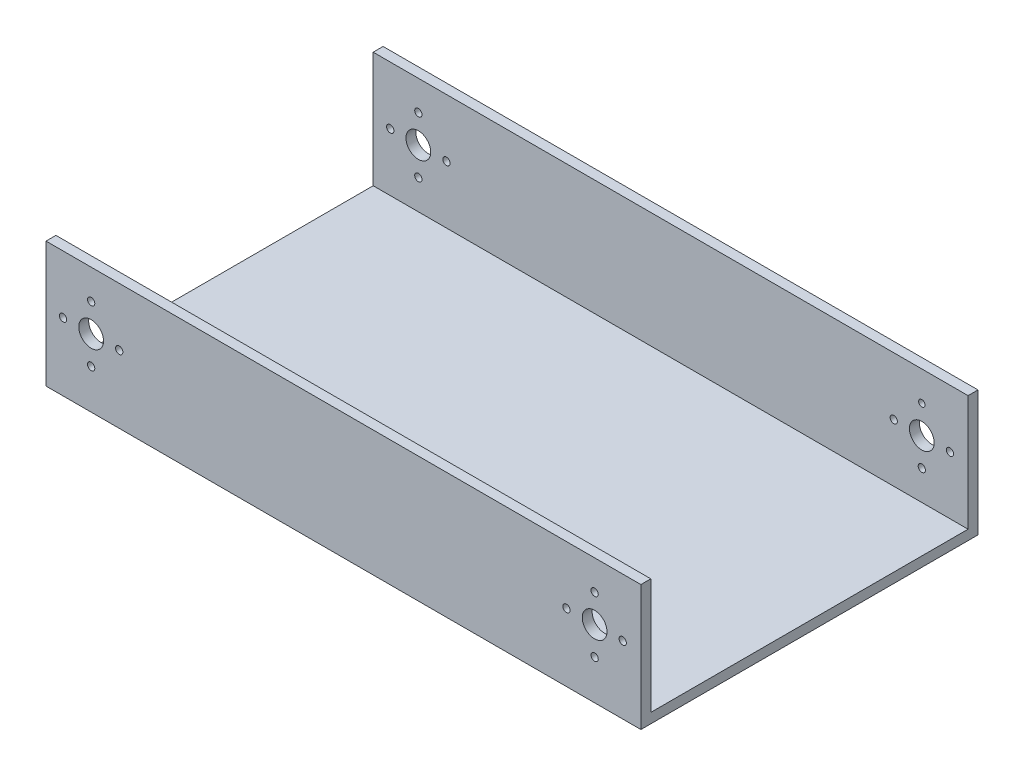
SolidWorks part; units mm, degrees
ref_plane "Front Plane" through (0, 0, 0) normal (0, 0, 1) x (1, 0, 0)
ref_plane "Top Plane" through (0, 0, 0) normal (0, 1, 0) x (1, 0, 0)
ref_plane "Right Plane" through (0, 0, 0) normal (1, 0, 0) x (0, 0, -1)
sketch "스케치1" plane through (0, 0, 0) normal (0, 0, 1) x (1, 0, 0)
  line L1 (-90, 17.5) -> (90, 17.5)
  line L2 (-90, 17.5) -> (-90, -17.5)
  line L3 (-90, -17.5) -> (90, -17.5)
  line L4 (90, 17.5) -> (90, -17.5)
  dimension "D1" = 17.5
  dimension "D2" = 35
  dimension "D3" = 90
  dimension "D4" = 180
extrude "보스-돌출1" add sketch "스케치1" along normal blind 3
sketch "스케치2" plane through (0, 0, 3) normal (0, 0, 1) x (1, 0, 0)
  line L0 (0, 0) -> (50000, 0) construction
  line L1 (0, 0) -> (0, -50000) construction
  line L2 (-76, 0) -> (-76, -50000) construction
  line L3 (76, 0) -> (76, -50000) construction
  circle A0 centre (-76.34, 0) radius 3.75
  circle A1 centre (76, 0) radius 3.75
  dimension "D1" = 76
  dimension "D2" = 76
extrude "컷-돌출1" cut sketch "스케치2" against normal blind 3
sketch "스케치3" plane through (0, 0, 3) normal (0, 0, 1) x (1, 0, 0)
  line L0 (-76.34, 0) -> (-76.34, 50000) construction
  line L1 (76, 0) -> (76, 50000) construction
  line L2 (-76.34, 0) -> (49923.66, 0) construction
  circle A0 centre (-76.34, 0) radius 8.5 construction
  circle A1 centre (76, 0) radius 8.5 construction
  circle A2 centre (-76.34, 8.5) radius 1.1
  circle A3 centre (-76.34, -8.5) radius 1.1
  circle A4 centre (-84.84, 0) radius 1.1
  circle A5 centre (-67.84, 0) radius 1.1
  circle A6 centre (76, 8.5) radius 1.1
  circle A7 centre (76, -8.5) radius 1.1
  circle A8 centre (67.5, 0) radius 1.1
  circle A9 centre (84.5, 0) radius 1.1
extrude "컷-돌출2" cut sketch "스케치3" against normal blind 3
sketch "스케치4" plane through (0, -17.5, 0) normal (0, -1, 0) x (1, 0, 0)
  line L0 (-90, 0) -> (-90, 50000) construction
  line L1 (90, 0) -> (90, 50000) construction
  line L2 (-100, 3) -> (49900, 3) construction
  line L6 (-100, -96) -> (49900, -96) construction
  line L7 (-100, -99) -> (49900, -99) construction
  line L8 (-100, 0) -> (49900, 0) construction
  line L11 (90, 3) -> (-90, 3)
  line L12 (90, 3) -> (90, -99)
  line L13 (90, -99) -> (-90, -99)
  line L14 (-90, 3) -> (-90, -99)
  dimension "D1" = 3
  dimension "D2" = 96
extrude "보스-돌출2" add sketch "스케치4" along normal blind 3
sketch "스케치5" plane through (0, -17.5, 0) normal (0, 1, 0) x (1, 0, 0)
  line L0 (-100, 99) -> (49900, 99) construction
  line L1 (86.532, 96) -> (50086.532, 96) construction
  line L2 (-90, 0) -> (-90, 50000) construction
  line L3 (-90, 0) -> (-90, 99) construction
  line L4 (90, 0) -> (90, 50000) construction
  line L7 (-90, 99) -> (90, 99)
  line L8 (-90, 99) -> (-90, 96)
  line L9 (-90, 96) -> (90, 96)
  line L10 (90, 99) -> (90, 96)
  dimension "D1" = 3
extrude "보스-돌출3" add sketch "스케치5" along normal blind 35
sketch "스케치6" plane through (0, 0, -99) normal (0, 0, -1) x (-1, 0, 0)
  circle A0 centre (-76, 0) radius 3.75
  circle A1 centre (76.34, 0) radius 3.75
  circle A2 centre (-76, -8.5) radius 1.1
  circle A3 centre (-67.5, 0) radius 1.1
  circle A4 centre (-76, 8.5) radius 0.9817
  circle A5 centre (-84.5, 0) radius 1.1
  circle A6 centre (84.84, 0) radius 1.1
  circle A7 centre (76.34, 8.5) radius 1.1
  circle A8 centre (67.84, 0) radius 1.1
  circle A9 centre (76.34, -8.5) radius 1.1
extrude "컷-돌출3" cut sketch "스케치6" against normal blind 35
